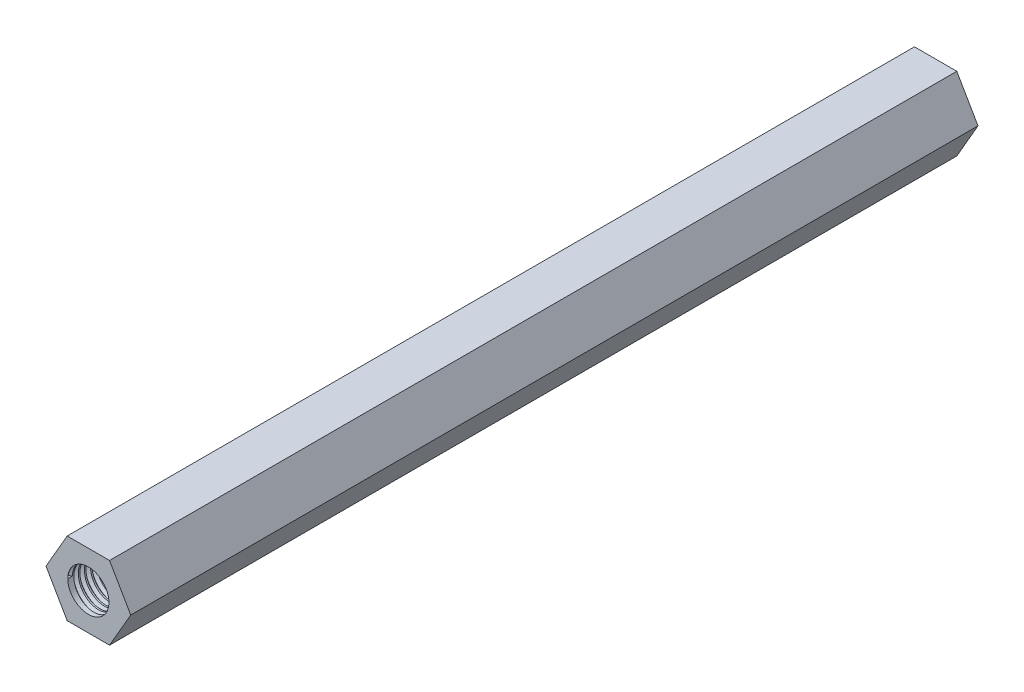
SolidWorks part; units mm, degrees
material "1.7036 (28CrS4)"
ref_plane "Plan de face" through (0, 0, 0) normal (0, 0, 1) x (1, 0, 0)
ref_plane "Plan de dessus" through (0, 0, 0) normal (0, 1, 0) x (1, 0, 0)
ref_plane "Plan de droite" through (0, 0, 0) normal (1, 0, 0) x (0, 0, -1)
sketch "Esquisse1" plane through (0, 0, 0) normal (0, 0, 1) x (1, 0, 0)
  line L0 (0, 3.5) -> (7, 3.5) construction
  line L1 (0, 0) -> (7, 0) construction
  line L2 (0, 0) -> (0, 7) construction
  line L3 (0, 7) -> (7, 7) construction
  line L4 (7, 0) -> (7, 7) construction
  line L5 (3.5, 7) -> (3.5, 0) construction
  line L7 (5.25, 0.4689) -> (7, 3.5)
  line L8 (7, 3.5) -> (5.25, 6.5311)
  line L9 (5.25, 6.5311) -> (1.75, 6.5311)
  line L10 (1.75, 6.5311) -> (0, 3.5)
  line L11 (0, 3.5) -> (1.75, 0.4689)
  line L12 (1.75, 0.4689) -> (5.25, 0.4689)
  circle A0 centre (3.5, 3.5) radius 3.5 construction
  dimension "D3" = 7
  dimension "D1" = 7
  dimension "D2" = 7
extrude "Boss.-Extru.1" add sketch "Esquisse1" along normal blind 70
sketch "Esquisse2" plane through (0, 0, 70) normal (0, 0, 1) x (1, 0, 0)
  line L0 (3.5, 6.5311) -> (3.5, 0.4689) construction
  line L1 (0.875, 1.9845) -> (6.125, 5.0155) construction
  line L6 (1.75, 0.4689) -> (5.25, 0.4689)
  line L7 (5.25, 0.4689) -> (7, 3.5)
  line L8 (7, 3.5) -> (5.25, 6.5311)
  line L9 (5.25, 6.5311) -> (1.75, 6.5311)
  line L10 (1.75, 6.5311) -> (0, 3.5)
  line L11 (0, 3.5) -> (1.75, 0.4689)
  line L12 (1.75, 0.4689) -> (5.25, 0.4689)
  line L13 (5.25, 0.4689) -> (7, 3.5)
  line L14 (7, 3.5) -> (5.25, 6.5311)
  line L15 (5.25, 6.5311) -> (1.75, 6.5311)
  line L16 (1.75, 6.5311) -> (0, 3.5)
  line L17 (0, 3.5) -> (1.75, 0.4689)
  circle A0 centre (3.5, 3.5) radius 1.5
  dimension "D2" = 3
  dimension "D1" = 0
hole_wizard "Dégagement M31" positions "Esquisse6" profile "Esquisse7" hole size "M3" standard "ISO"
sketch "Esquisse6" plane through (0, 0, 70) normal (0, 0, 1) x (1, 0, 0)
  point P0 (3.5, 3.5)
sketch "Esquisse7" plane through (3.5, 3.5, 70) normal (1, 0, 0) x (0, -1, 0)
  line L0 (0, 0) -> (0, 9.0215)
  line L1 (0, 9.0215) -> (1.7, 8)
  line L2 (1.7, 8) -> (1.7, 0)
  line L5 (1.7, 0) -> (0, 0)
  line L10 (0, 9.0215) -> (-1.7, 8) construction
  line L11 (0, -6.35) -> (0, 107.95) construction
  dimension "Diamètre du perçage" = 3.4
  dimension "Profondeur du perçage" = 8
  dimension "Angle de pointe" = 118
thread "Filetage1" pitch 0.5 method cut profile "Profil de filetage1" start angle 0, offset 0, length 10, pitch 0.5, diameter 3.4
ref_plane "Plan1" through (1.8, 3.5, 70) normal (0, -1, 0) x (-1, 0, 0)
sketch "Profil de filetage1" plane through (1.8, 3.5, 70) normal (0, -1, 0) x (-1, 0, 0)
  line L0 (0, 0) -> (0, 0.5) construction
  line L1 (0, 0) -> (0.2706, 0.1562)
  line L2 (0.2706, 0.1562) -> (0.2706, 0.2187)
  line L3 (0.2706, 0.2187) -> (0, 0.375)
  line L4 (0.2706, 0.1875) -> (0, 0.1875) construction
  line L11 (0, 0) -> (0, 0.375)
  point P2 (0, 0)
  dimension "Pitch" = 0.5
  dimension "Profile_Angle" = 60
  dimension "Profile_Land" = 0.0625
  dimension "Profile_Height" = 0.2706
hole_wizard "Dégagement M32" positions "Esquisse10" profile "Esquisse11" hole size "M3" standard "ISO"
sketch "Esquisse10" plane through (0, 0, 0) normal (0, 0, -1) x (-1, 0, 0)
  point P0 (-3.5, 3.5)
sketch "Esquisse11" plane through (3.5, 3.5, 0) normal (1, 0, 0) x (0, 1, 0)
  line L0 (0, 0) -> (0, 11.0215)
  line L1 (0, 11.0215) -> (1.7, 10)
  line L2 (1.7, 10) -> (1.7, 0)
  line L5 (1.7, 0) -> (0, 0)
  line L10 (0, 11.0215) -> (-1.7, 10) construction
  line L11 (0, -6.35) -> (0, 107.95) construction
  dimension "Diamètre du perçage" = 3.4
  dimension "Profondeur du perçage" = 10
  dimension "Angle de pointe" = 118
equation "\"diam_cercle_circons\"= 7mm"
equation "\"D1@Esquisse1\"=\"diam_cercle_circons\""
equation "\"D2@Esquisse1\"=\"diam_cercle_circons\""
equation "\"Hauteur\"= 70"
equation "\"D1@Boss.-Extru.1\"=\"Hauteur\""
equation "\"D3@Esquisse1\"=\"diam_cercle_circons\""
